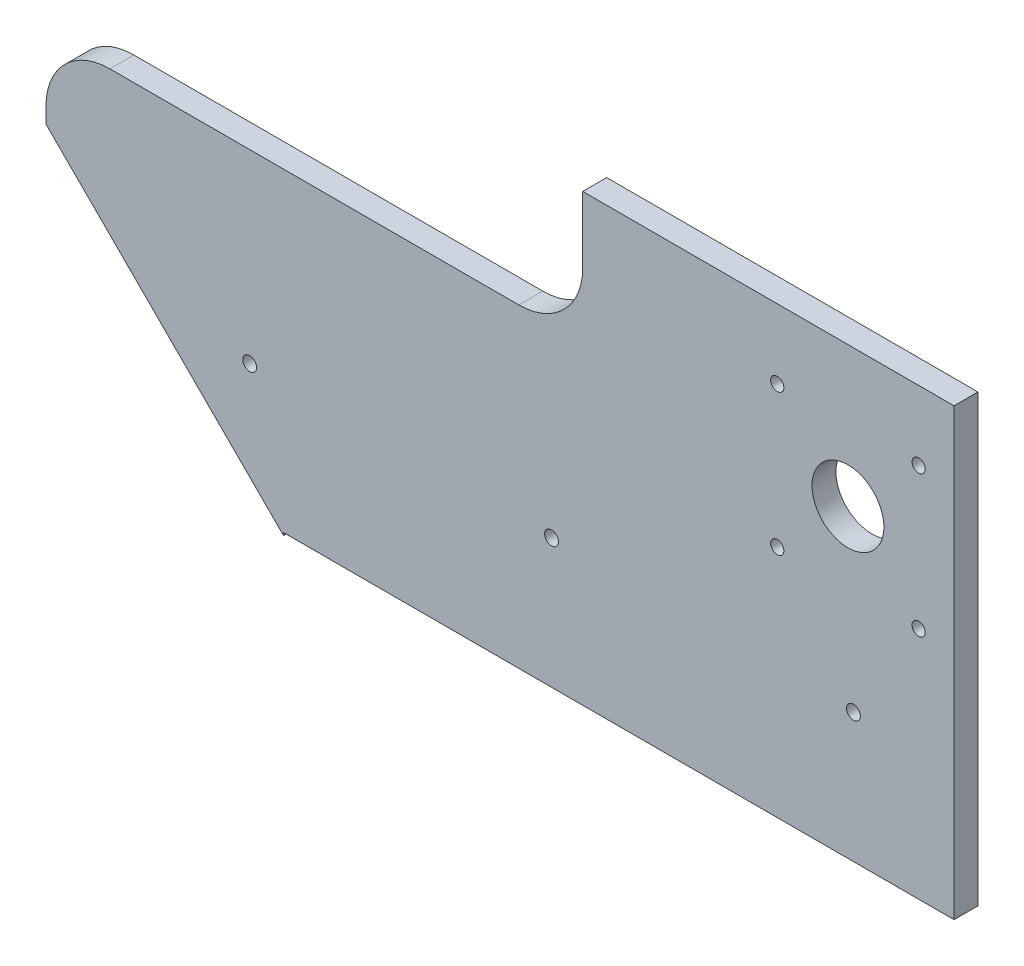
SolidWorks part; units mm, degrees
ref_plane "Front Plane" through (0, 0, 0) normal (0, 0, 1) x (1, 0, 0)
ref_plane "Top Plane" through (0, 0, 0) normal (0, 1, 0) x (1, 0, 0)
ref_plane "Right Plane" through (0, 0, 0) normal (1, 0, 0) x (0, 0, -1)
sketch "Sketch1" plane through (0, 0, 0) normal (0, 0, 1) x (1, 0, 0)
  line L0 (-138.2594, 48.9915) -> (32.2106, -121.4785)
  line L1 (32.2106, -121.4785) -> (222.7106, -121.4785)
  line L2 (-138.2594, 146.2068) -> (-138.2594, 48.9915)
  line L3 (-138.2594, 146.2068) -> (222.7106, 146.2068)
  line L4 (222.7106, -121.4785) -> (222.7106, 146.2068)
  circle A0 centre (180.538, 76.832) radius 14.2875
  circle A2 centre (180.538, 76.832) radius 69.85 construction
  circle A3 centre (180.538, 76.832) radius 318.7974 construction
  point P0 (0, 0)
  point P2 (180.538, 76.832)
  dimension "D4" = 198.3105
  dimension "D1" = 45
  dimension "D2" = 267.6854
  dimension "D5" = 245.11
extrude "Boss-Extrude1" add sketch "Sketch1" along normal blind 9.525
sketch "Sketch2" plane through (0, 0, 9.525) normal (0, 0, 1) x (1, 0, 0)
  line L0 (32.2106, -121.4785) -> (222.7106, -121.4785) construction
  line L1 (241.7606, -121.4785) -> (-43.8123, -121.4785)
  line L2 (241.7606, -121.4785) -> (241.7606, -44.3895)
  line L3 (241.7606, -44.3895) -> (-43.8123, -44.3895)
  line L4 (-43.8123, -121.4785) -> (-43.8123, -44.3895)
extrude "Cut-Extrude1" cut sketch "Sketch2" against normal through all contours L3 L4 L1 L2
sketch "Sketch4" plane through (0, 0, 9.525) normal (0, 0, 1) x (1, 0, 0)
  line L1 (-138.2594, 146.2068) -> (-138.2594, 48.9915) construction
  line L3 (-138.2594, 146.2068) -> (75.1006, 146.2068)
  line L4 (-138.2594, 146.2068) -> (-138.2594, 80.7415)
  line L5 (-138.2594, 80.7415) -> (75.1006, 80.7415)
  line L6 (75.1006, 146.2068) -> (75.1006, 80.7415)
extrude "Cut-Extrude2" cut sketch "Sketch4" against normal through all contours L5 L6 L3 L4
fillet "Fillet2" radius 25.4 2 edges at (-138.2594, 80.7415, 4.7625) (75.1006, 80.7415, 4.7625)
hole_wizard "Ø5.5 (5.5) Diameter Hole1" positions "Sketch15" profile "Sketch14" hole size "Ø5.5" standard "ANSI Metric" end condition through all
sketch "Sketch15" plane through (0, 0, 0) normal (0, 0, -1) x (-1, 0, 0)
  line L2 (-222.7106, -44.3895) -> (-222.7106, 146.2068) construction
  point P3 (-182.7106, 7.0429)
  point P6 (-62.7106, 7.0429)
  point P9 (57.2894, 7.0429)
  dimension "D1" = 40
  dimension "D2" = 120
  dimension "D3" = 120
sketch "Sketch14" plane through (182.7106, 7.0429, 0) normal (1, 0, 0) x (0, 1, 0)
  line L0 (0, 0) -> (0, 9.525)
  line L1 (0, 9.525) -> (2.75, 9.525)
  line L2 (2.75, 9.525) -> (2.75, 0)
  line L5 (2.75, 0) -> (0, 0)
  line L11 (0, -6.35) -> (0, 107.95) construction
  dimension "Thru Hole Dia." = 5.5
  dimension "Thru Hole Depth" = 9.525
sketch "Sketch16" plane through (222.7106, 0, 0) normal (1, 0, 0) x (0, 0, -1)
  line L0 (0, -44.3895) -> (0, 146.2068) construction
  line L1 (-9.525, 146.2068) -> (0, 146.2068)
  line L2 (-9.525, 146.2068) -> (-9.525, 145.2215)
  line L3 (-9.525, 145.2215) -> (0, 145.2215)
  line L4 (0, 146.2068) -> (0, 145.2215)
extrude "Cut-Extrude3" cut sketch "Sketch16" against normal through all
sketch "Sketch17" plane through (0, 0, 0) normal (0, 0, -1) x (-1, 0, 0)
  line L0 (-222.7106, -44.3895) -> (-222.7106, 145.2215) construction
  line L1 (-75.1006, 145.2215) -> (-222.7106, 145.2215)
  line L2 (-75.1006, 145.2215) -> (-75.1006, 132.5215)
  line L3 (-75.1006, 132.5215) -> (-222.7106, 132.5215)
  line L4 (-222.7106, 145.2215) -> (-222.7106, 132.5215)
  dimension "D1" = 12.7
extrude "Cut-Extrude4" cut sketch "Sketch17" against normal through all
hole_wizard "Tap Drill for M6x0.75 Tap1" positions "Sketch19" profile "Sketch18" hole size "M6x0.75" standard "Lanco STD" end condition through all
sketch "Sketch19" plane through (0, 0, 9.525) normal (0, 0, 1) x (1, 0, 0)
  point P0 (208.638, 104.932)
  point P3 (152.438, 104.932)
  point P6 (152.438, 48.732)
  point P9 (208.638, 48.732)
sketch "Sketch18" plane through (208.638, 104.932, 9.525) normal (1, 0, 0) x (0, -1, 0)
  line L0 (0, 0) -> (0, 9.525)
  line L1 (0, 9.525) -> (2.625, 9.525)
  line L2 (2.625, 9.525) -> (2.625, 0)
  line L5 (2.625, 0) -> (0, 0)
  line L11 (0, -6.35) -> (0, 107.95) construction
  dimension "Thru Hole Dia." = 5.25
  dimension "Thru Hole Depth" = 9.525
